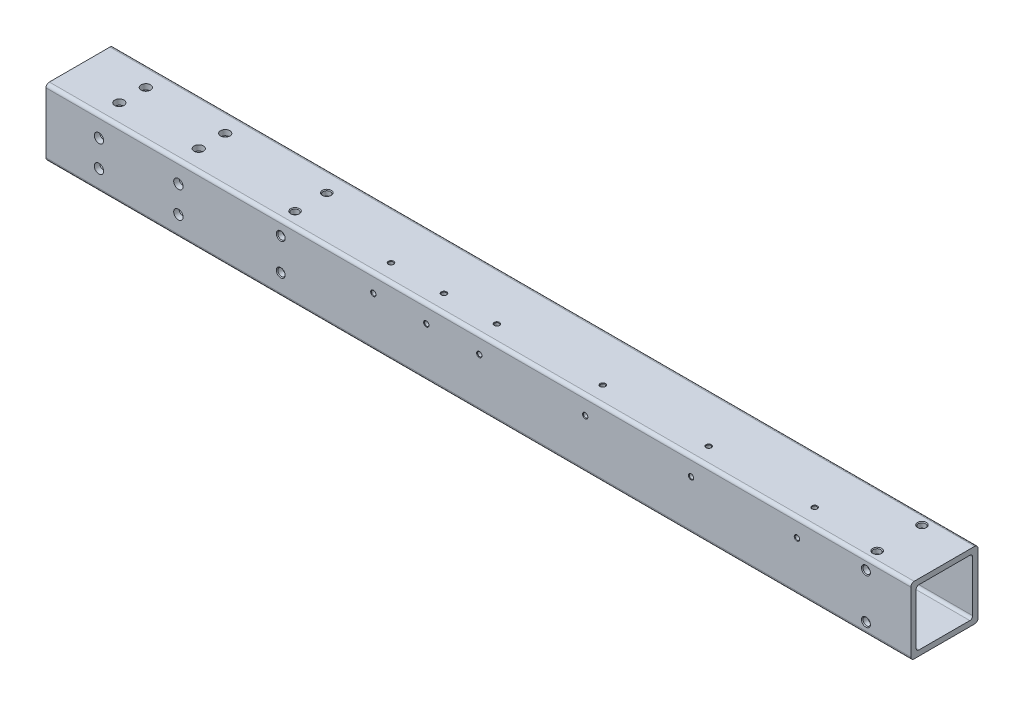
SolidWorks part; units mm, degrees
material "ASTM A36 Steel"
ref_plane "Front" through (0, 0, 0) normal (0, 0, 1) x (1, 0, 0)
ref_plane "Top" through (0, 0, 0) normal (0, 1, 0) x (1, 0, 0)
ref_plane "Right" through (0, 0, 0) normal (1, 0, 0) x (0, 0, -1)
sketch "Sketch1" plane through (0, 0, 0) normal (1, 0, 0) x (0, 0, -1)
  line L0 (-16.002, 0) -> (-19.05, 0) construction
  line L1 (17.145, -19.05) -> (-17.145, -19.05) construction
  line L2 (19.05, -17.145) -> (19.05, 17.145) construction
  line L3 (17.145, 19.05) -> (-17.145, 19.05) construction
  line L4 (-19.05, -17.145) -> (-19.05, 17.145) construction
  line L5 (19.05, -19.05) -> (-19.05, 19.05) construction
  line L6 (19.05, 19.05) -> (-19.05, -19.05) construction
  line L7 (14.4018, 16.002) -> (-14.4018, 16.002) construction
  line L8 (16.002, 14.4018) -> (16.002, -14.4018) construction
  line L9 (14.4018, -16.002) -> (-14.4018, -16.002) construction
  line L10 (-16.002, 14.4018) -> (-16.002, -14.4018) construction
  line L11 (16.002, 16.002) -> (-16.002, -16.002) construction
  line L12 (16.002, -16.002) -> (-16.002, 16.002) construction
  line L13 (0, -16.002) -> (0, -19.05) construction
  line L14 (16.002, -14.4018) -> (16.002, -19.05) construction
  line L15 (16.002, 0) -> (19.05, 0) construction
  line L16 (16.002, -19.05) -> (19.05, -19.05) construction
  arc A0 (-14.4018, -16.002) -> (-16.002, -14.4018) centre (-14.4018, -14.4018) cw construction
  arc A1 (16.002, -14.4018) -> (14.4018, -16.002) centre (14.4018, -14.4018) cw construction
  arc A2 (14.4018, 16.002) -> (16.002, 14.4018) centre (14.4018, 14.4018) cw construction
  arc A3 (-14.4018, 16.002) -> (-16.002, 14.4018) centre (-14.4018, 14.4018) ccw construction
  arc A4 (17.145, -19.05) -> (19.05, -17.145) centre (17.145, -17.145) ccw construction
  arc A5 (19.05, 17.145) -> (17.145, 19.05) centre (17.145, 17.145) ccw construction
  arc A6 (-17.145, 19.05) -> (-19.05, 17.145) centre (-17.145, 17.145) ccw construction
  arc A7 (-17.145, -19.05) -> (-19.05, -17.145) centre (-17.145, -17.145) cw construction
  point P0 (0, 0)
  point P6 (0, 0)
  dimension "D2" = 1.6002
  dimension "D3" = 1.905
  dimension "Outside Width" = 38.1
  dimension "Ouside Height" = 38.1
  dimension "Inside Height" = 32.004
  dimension "Wall Thickness" = 3.048
sketch "Sketch2" plane through (0, 0, 0) normal (0, 0, 1) x (1, 0, 0)
  line L0 (-245, 0) -> (245, 0) construction
  point P3 (-209.948, 0)
  point P4 (209.948, 0)
  dimension "Length" = 490
  dimension "D1" = 35.052
  dimension "D2" = 35.052
sketch "Sketch4" plane through (0, 0, 0) normal (1, 0, 0) x (0, 0, -1)
  line L8 (19.05, -17.145) -> (19.05, 17.145)
  line L9 (17.145, 19.05) -> (-17.145, 19.05)
  line L10 (-19.05, -17.145) -> (-19.05, 17.145)
  line L11 (17.145, -19.05) -> (-17.145, -19.05)
  line L12 (16.002, 14.4018) -> (16.002, -14.4018)
  line L13 (14.4018, -16.002) -> (-14.4018, -16.002)
  line L14 (-16.002, 14.4018) -> (-16.002, -14.4018)
  line L15 (14.4018, 16.002) -> (-14.4018, 16.002)
  arc A8 (19.05, 17.145) -> (17.145, 19.05) centre (17.145, 17.145) ccw
  arc A9 (-17.145, 19.05) -> (-19.05, 17.145) centre (-17.145, 17.145) ccw
  arc A10 (-19.05, -17.145) -> (-17.145, -19.05) centre (-17.145, -17.145) ccw
  arc A11 (17.145, -19.05) -> (19.05, -17.145) centre (17.145, -17.145) ccw
  arc A12 (14.4018, -16.002) -> (16.002, -14.4018) centre (14.4018, -14.4018) ccw
  arc A13 (-16.002, -14.4018) -> (-14.4018, -16.002) centre (-14.4018, -14.4018) ccw
  arc A14 (-14.4018, 16.002) -> (-16.002, 14.4018) centre (-14.4018, 14.4018) ccw
  arc A15 (16.002, 14.4018) -> (14.4018, 16.002) centre (14.4018, 14.4018) ccw
extrude "Boss-Extrude1" add sketch "Sketch4" along normal up to vertex (-245 mm away) and the other way up to vertex (-245 mm away) up to point (-245, 0, 0) other way up to point (245, 0, 0)
hole_wizard "M5x0.8 Tapped Hole1" positions "Sketch5" profile "Sketch6" tap size "M5x0.8" standard "ANSI Metric" end condition up to next
sketch "Sketch5" plane through (0, 19.05, 0) normal (0, 1, 0) x (1, 0, 0)
  line L0 (-112, -10.95) -> (-112, 7.05) construction
  line L2 (-245, 17.145) -> (-245, -17.145) construction
  line L3 (245, 19.05) -> (-245, 19.05) construction
  point P0 (-112, 7.05)
  point P2 (-112, -10.95)
  point P20 (-112, -1.95)
  dimension "D1" = 18
  dimension "D2" = 133
  dimension "D3" = 21
sketch "Sketch6" plane through (-112, 19.05, -7.05) normal (1, 0, 0) x (0, 0, 1)
  line L0 (0, 0) -> (0, 3.048)
  line L1 (0, 3.048) -> (2.1, 3.048)
  line L2 (2.1, 3.048) -> (2.1, 0.425)
  line L3 (2.1, 0.425) -> (2.525, 0)
  line L5 (2.525, 0) -> (0, 0)
  line L6 (-2.1, 0.425) -> (-2.525, 0) construction
  line L11 (0, -6.35) -> (0, 107.95) construction
  dimension "Thru Tap Drill Dia." = 4.2
  dimension "Thru Tap Drill Depth" = 3.048
  dimension "Near C'Sink Dia." = 5.05
  dimension "Near C'Sink Angle" = 90
cosmetic thread "Hole Thread7" parameters "D2"=5
cosmetic thread "Hole Thread8" parameters "D2"=5
ref_plane "Plane1" through (0, 0, 0) normal (0, -0.7071, 0.7071) x (1, 0, 0)
hole_wizard "M3x0.5 Tapped Hole1" positions "Sketch8" profile "Sketch9" tap size "M3x0.5" standard "ANSI Metric" end condition up to next
sketch "Sketch8" plane through (0, 0, 19.05) normal (0, 0, 1) x (1, 0, 0)
  line L0 (245, 17.145) -> (245, -17.145) construction
  line L1 (245, 19.05) -> (-245, 19.05) construction
  line L3 (-59.5, 9.05) -> (0.5, 9.05) construction
  point P0 (180.5, 9.05)
  point P5 (120.5, 9.05)
  point P6 (60.5, 9.05)
  point P7 (0.5, 9.05)
  point P8 (-59.5, 9.05)
  point P27 (-29.5, 9.05)
  dimension "D2" = 60
  dimension "D3" = 64.5
  dimension "D4" = 10
  dimension "D1" = 5
sketch "Sketch9" plane through (180.5, 9.05, 19.05) normal (1, 0, 0) x (0, -1, 0)
  line L0 (0, 0) -> (0, 3.048)
  line L1 (0, 3.048) -> (1.25, 3.048)
  line L2 (1.25, 3.048) -> (1.25, 0.275)
  line L3 (1.25, 0.275) -> (1.525, 0)
  line L5 (1.525, 0) -> (0, 0)
  line L6 (-1.25, 0.275) -> (-1.525, 0) construction
  line L11 (0, -6.35) -> (0, 107.95) construction
  dimension "Thru Tap Drill Dia." = 2.5
  dimension "Thru Tap Drill Depth" = 3.048
  dimension "Near C'Sink Dia." = 3.05
  dimension "Near C'Sink Angle" = 90
cosmetic thread "Hole Thread1" parameters "D2"=3
cosmetic thread "Hole Thread2" parameters "D2"=3
cosmetic thread "Hole Thread3" parameters "D2"=3
cosmetic thread "Hole Thread4" parameters "D2"=3
cosmetic thread "Hole Thread5" parameters "D2"=3
cosmetic thread "Hole Thread6" parameters "D2"=3
hole_wizard "M5x0.8 Tapped Hole2" positions "Sketch21" profile "Sketch22" tap size "M5x0.8" standard "ANSI Metric" end condition up to next
sketch "Sketch21" plane through (0, 0, 19.05) normal (0, 0, 1) x (1, 0, 0)
  line L0 (219.6, 12.7) -> (219.6, -12.7) construction
  line L2 (245, 17.145) -> (245, -17.145) construction
  point P0 (219.6, 12.7)
  point P2 (219.6, -12.7)
  point P11 (245, 0)
  point P12 (219.6, 0)
  dimension "D1" = 25.4
  dimension "D2" = 25.4
sketch "Sketch22" plane through (219.6, 12.7, 19.05) normal (1, 0, 0) x (0, -1, 0)
  line L0 (0, 0) -> (0, 3.048)
  line L1 (0, 3.048) -> (2.1, 3.048)
  line L2 (2.1, 3.048) -> (2.1, 0.425)
  line L3 (2.1, 0.425) -> (2.525, 0)
  line L5 (2.525, 0) -> (0, 0)
  line L6 (-2.1, 0.425) -> (-2.525, 0) construction
  line L11 (0, -6.35) -> (0, 107.95) construction
  dimension "Thru Tap Drill Dia." = 4.2
  dimension "Thru Tap Drill Depth" = 3.048
  dimension "Near C'Sink Dia." = 5.05
  dimension "Near C'Sink Angle" = 90
cosmetic thread "Hole Thread9" parameters "D2"=5
cosmetic thread "Hole Thread10" parameters "D2"=5
mirror "Mirror1" about plane through (0, 0, 0) normal (0, -0.7071, 0.7071) of "M5x0.8 Tapped Hole2", "M5x0.8 Tapped Hole1", "M3x0.5 Tapped Hole1"
ref_plane "Plane2" through (0, 0, 0) normal (0, 0.7071, 0.7071) x (1, 0, 0)
sketch "Sketch12" plane through (0, 19.05, 0) normal (0, 1, 0) x (1, 0, 0)
  line L0 (-215, -7.5) -> (-215, 7.5) construction
  line L1 (-245, 0) -> (-215, 0) construction
  line L4 (-245, 17.145) -> (-245, -17.145) construction
  dimension "D1" = 30
  dimension "D2" = 15
hole_wizard "M5 Clearance Hole1" positions "Sketch13" profile "Sketch15" hole size "M5" standard "ANSI Metric" end condition up to next
sketch "Sketch13" plane through (0, 19.05, 0) normal (0, 1, 0) x (1, 0, 0)
  point P0 (-215, 7.5)
  point P3 (-215, -7.5)
  point P6 (-170, -7.5)
  point P8 (-170, 7.5)
  dimension "D1" = 45
sketch "Sketch15" plane through (-215, 19.05, -7.5) normal (1, 0, 0) x (0, 0, 1)
  line L0 (0, 0) -> (0, 3.048)
  line L1 (0, 3.048) -> (2.65, 3.048)
  line L2 (2.65, 3.048) -> (2.65, 0)
  line L5 (2.65, 0) -> (0, 0)
  line L11 (0, -6.35) -> (0, 107.95) construction
  dimension "Thru Hole Dia." = 5.3
  dimension "Thru Hole Depth" = 3.048
hole_wizard "M5x0.8 Tapped Hole3" positions "Sketch23" profile "Sketch24" tap size "M5x0.8" standard "ANSI Metric" end condition up to next
sketch "Sketch23" plane through (0, 0, -19.05) normal (0, 0, -1) x (-1, 0, 0)
  line L0 (-245, -19.05) -> (245, -19.05) construction
  line L2 (-245, -17.145) -> (-245, 17.145) construction
  point P0 (-250, -9.05)
  point P12 (-190, -9.05)
  point P13 (-130, -9.05)
  point P14 (-70, -9.05)
  point P15 (-10, -9.05)
  point P16 (50, -9.05)
  point P17 (110, -9.05)
  point P18 (170, -9.05)
  point P19 (230, -9.05)
  dimension "D1" = 10
  dimension "D2" = 5
  dimension "D4" = 60
  dimension "D3" = 9
sketch "Sketch24" plane through (250, -9.05, -19.05) normal (1, 0, 0) x (0, 1, 0)
  line L0 (0, 0) -> (0, 38.1)
  line L1 (0, 38.1) -> (2.1, 38.1)
  line L2 (2.1, 38.1) -> (2.1, 0.425)
  line L3 (2.1, 0.425) -> (2.525, 0)
  line L5 (2.525, 0) -> (0, 0)
  line L6 (-2.1, 0.425) -> (-2.525, 0) construction
  line L11 (0, -6.35) -> (0, 107.95) construction
  dimension "Thru Tap Drill Dia." = 4.2
  dimension "Thru Tap Drill Depth" = 38.1
  dimension "Near C'Sink Dia." = 5.05
  dimension "Near C'Sink Angle" = 90
cosmetic thread "Hole Thread11" parameters "D2"=5
cosmetic thread "Hole Thread12" parameters "D1"=3.048, "D2"=5
cosmetic thread "Hole Thread13" parameters "D2"=5
cosmetic thread "Hole Thread14" parameters "D2"=5
cosmetic thread "Hole Thread15" parameters "D2"=5
cosmetic thread "Hole Thread16" parameters "D2"=5
cosmetic thread "Hole Thread17" parameters "D2"=5
mirror "Mirror2" about plane through (0, 0, 0) normal (0, -0.7071, 0.7071) of "M5x0.8 Tapped Hole3", "M5 Clearance Hole1"
hole_wizard "Ø10.0 (10) Diameter Hole1" positions "Sketch17" profile "Sketch18" hole size "Ø10.0" standard "ANSI Metric" end condition up to next
sketch "Sketch17" plane through (0, 0, -16.002) normal (0, 0, 1) x (1, 0, 0)
  point P0 (-215, -7.5)
  point P3 (-215, 7.5)
  point P6 (-170, 7.5)
  point P9 (-170, -7.5)
sketch "Sketch18" plane through (-215, -7.5, -16.002) normal (1, 0, 0) x (0, -1, 0)
  line L0 (0, 0) -> (0, 3.048)
  line L1 (0, 3.048) -> (5, 3.048)
  line L2 (5, 3.048) -> (5, 0)
  line L5 (5, 0) -> (0, 0)
  line L11 (0, -6.35) -> (0, 107.95) construction
  dimension "Thru Hole Dia." = 10
  dimension "Thru Hole Depth" = 3.048
hole_wizard "Ø10.0 (10) Diameter Hole2" positions "Sketch19" profile "Sketch20" hole size "Ø10.0" standard "ANSI Metric" end condition up to next
sketch "Sketch19" plane through (0, -16.002, 0) normal (0, 1, 0) x (1, 0, 0)
  point P0 (-215, 7.5)
  point P3 (-215, -7.5)
  point P6 (-170, -7.5)
  point P9 (-170, 7.5)
sketch "Sketch20" plane through (-215, -16.002, -7.5) normal (1, 0, 0) x (0, 0, 1)
  line L0 (0, 0) -> (0, 3.048)
  line L1 (0, 3.048) -> (5, 3.048)
  line L2 (5, 3.048) -> (5, 0)
  line L5 (5, 0) -> (0, 0)
  line L11 (0, -6.35) -> (0, 107.95) construction
  dimension "Thru Hole Dia." = 10
  dimension "Thru Hole Depth" = 3.048
equation "\"D3@Sketch1\"=\"Outside Width@Sketch1\"*.05"
equation "\"D2@Sketch1\" = \"Inside Height@Sketch1\" * .05"
equation "\"D1@Sketch2\"=\"Outside Width@Sketch1\"-\"Wall Thickness@Sketch1\""
equation "\"D2@Sketch2\"=\"D1@Sketch2\""
